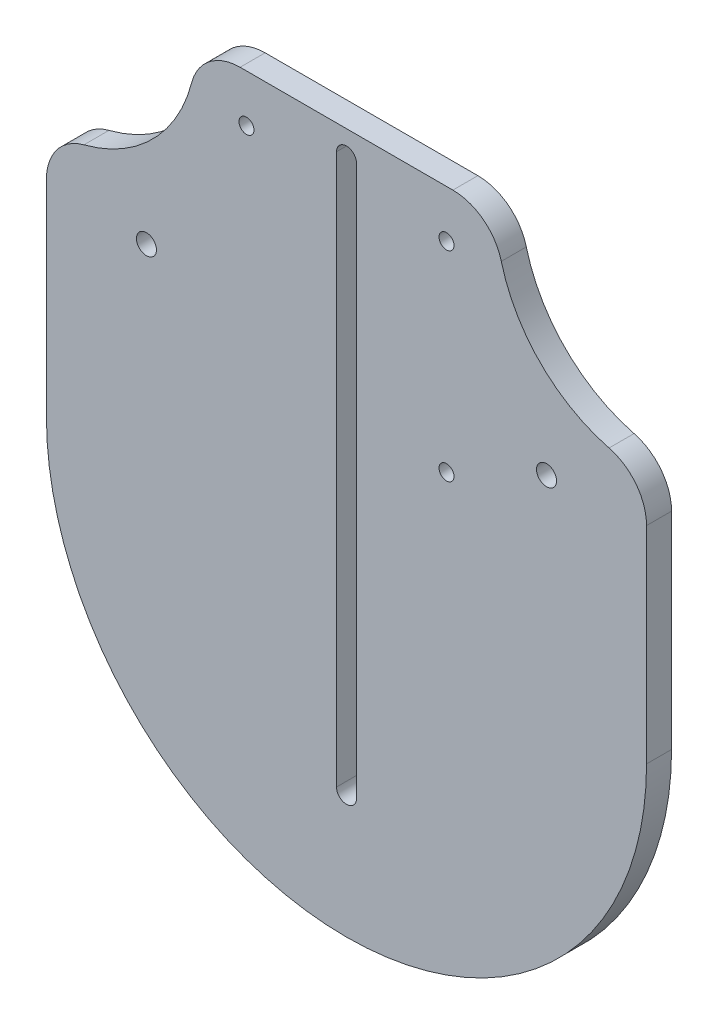
SolidWorks part; units mm, degrees
ref_plane "Alzado" through (0, 0, 0) normal (0, 0, 1) x (1, 0, 0)
ref_plane "Planta" through (0, 0, 0) normal (0, 1, 0) x (1, 0, 0)
ref_plane "Vista lateral" through (0, 0, 0) normal (1, 0, 0) x (0, 0, -1)
sketch "Croquis1" plane through (0, 0, 0) normal (0, 0, 1) x (1, 0, 0)
  line L1 (-60, -70) -> (60, -70)
  line L2 (-60, -70) -> (-60, 70)
  line L3 (-60, 70) -> (60, 70)
  line L4 (60, -70) -> (60, 70)
  line L5 (-60, -70) -> (60, 70) construction
  line L6 (-60, 70) -> (60, -70) construction
  point P0 (0, 0)
extrude "Saliente-Extruir1" add sketch "Croquis1" along normal blind 5
sketch "Croquis2" plane through (0, 0, 5) normal (0, 0, 1) x (1, 0, 0)
  line L0 (60, -70) -> (60, 70) construction
  line L1 (-60, 70) -> (-60, -70) construction
  line L2 (60, 70) -> (-60, 70) construction
  line L3 (60, 70) -> (-60, 70) construction
  circle A0 centre (-40, 30) radius 2
  circle A1 centre (40, 30) radius 2
  circle A2 centre (0, 65) radius 2
  circle A3 centre (0, -45) radius 2
  circle A4 centre (-20, 60.5) radius 1.5
  circle A5 centre (20, 60.5) radius 1.5
  circle A6 centre (20, 20.5) radius 1.5
  point P8 (0, 70)
  dimension "D1" = 20
  dimension "D5" = 110
  dimension "D7" = 40
  dimension "D2" = 20
  dimension "D3" = 40
  dimension "D4" = 40
  dimension "D6" = 5
  dimension "D8" = 0
  dimension "D9" = 40
  dimension "D10" = 20
  dimension "D11" = 4.5
extrude "Cortar-Extruir1" cut sketch "Croquis2" against normal up to surface (5 mm away) up to face at (0, 0, 0)
sketch "Croquis3" plane through (0, 0, 5) normal (0, 0, 1) x (1, 0, 0)
  line L1 (-2, 65) -> (2, 65)
  line L2 (-2, 65) -> (-2, -45)
  line L3 (-2, -45) -> (2, -45)
  line L4 (2, 65) -> (2, -45)
  circle A0 centre (0, 65) radius 2 construction
  circle A1 centre (0, -45) radius 2 construction
extrude "Cortar-Extruir2" cut sketch "Croquis3" against normal up to surface (5 mm away) up to face at (18.5, 20.5, 0)
sketch "Croquis5" plane through (0, 0, 5) normal (0, 0, 1) x (1, 0, 0)
  circle A1 centre (-60, 70) radius 30
  circle A2 centre (60, 70) radius 30
extrude "Cortar-Extruir3" cut sketch "Croquis5" against normal up to surface (5 mm away) up to face at (0, 10, 0)
fillet "Redondeo2" radius 10 4 edges at (-60, 40, 2.5) (60, 40, 2.5) (30, 70, 2.5) (-30, 70, 2.5)
fillet "Redondeo3" radius 60 2 edges at (60, -70, 2.5) (-60, -70, 2.5)
